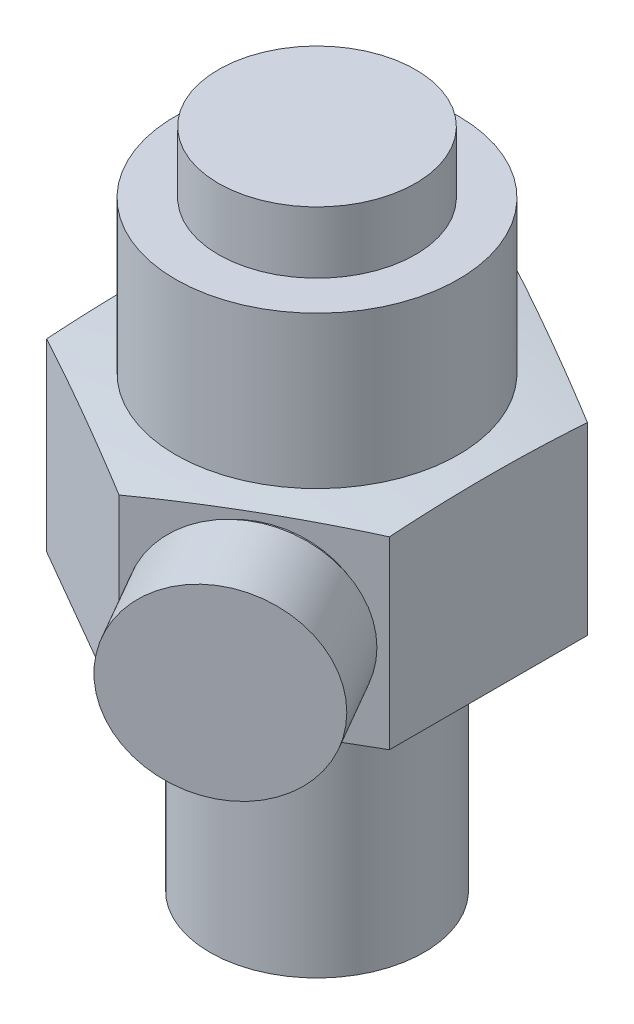
SolidWorks part; units mm, degrees
material "Brass"
ref_plane "Front Plane" through (0, 0, 0) normal (0, 0, 1) x (1, 0, 0)
ref_plane "Top Plane" through (0, 0, 0) normal (0, 1, 0) x (1, 0, 0)
ref_plane "Right Plane" through (0, 0, 0) normal (1, 0, 0) x (0, 0, -1)
sketch "Sketch1" plane through (0, 0, 0) normal (1, 0, 0) x (0, 0, -1)
  line L0 (10.4775, 33.1957) -> (10.4775, 44.45)
  line L1 (0, 0) -> (7.9375, 0)
  line L2 (0, 0) -> (0, 44.45)
  line L3 (0, 44.45) -> (10.4775, 44.45)
  line L4 (7.9375, 0) -> (7.9375, 19.05)
  line L5 (7.9375, 19.05) -> (25.4, 19.05)
  line L8 (25.4, 19.05) -> (25.4, 30.5116)
  arc A0 (10.4775, 33.1957) -> (25.4, 30.5116) centre (2.3997, -54.5366) cw
  dimension "D1" = 7.9375
  dimension "D2" = 19.05
  dimension "D5" = 10.4775
  dimension "D6" = 25.4
revolve "Revolve1" add sketch "Sketch1" angle 360 about L2
sketch "Sketch2" plane through (0, 0, 0) normal (0, 1, 0) x (1, 0, 0)
  line L0 (-12.7, 7.3323) -> (0, 14.6647)
  line L1 (0, 14.6647) -> (12.7, 7.3323)
  line L2 (12.7, 7.3323) -> (12.7, -7.3323)
  line L3 (12.7, -7.3323) -> (0, -14.6647)
  line L4 (0, -14.6647) -> (-12.7, -7.3323)
  line L5 (-12.7, 7.3323) -> (-12.7, -7.3323)
  line L6 (-12.7, 7.3323) -> (12.7, -7.3323) construction
  line L7 (-12.7, -7.3323) -> (12.7, 7.3323) construction
  line L8 (0, 14.6647) -> (0, -14.6647) construction
  circle A0 centre (0, 0) radius 12.7 construction
  circle A1 centre (0, 0) radius 31.2849
  dimension "D1" = 25.4
  dimension "D2" = 120
extrude "Cut-Extrude2" cut sketch "Sketch2" along normal through all
sketch "Sketch3" plane through (-6.35, 0, -10.9985) normal (-0.5, 0, -0.866) x (-0.866, 0, 0.5)
  circle A0 centre (0, 26.3074) radius 3.175
  dimension "D1" = 6.35
extrude "Boss-Extrude1" add sketch "Sketch3" along normal blind 6.35
sketch "Sketch4" plane through (6.35, 0, 10.9985) normal (0.5, 0, 0.866) x (0.866, 0, -0.5)
  circle A0 centre (0, 26.0448) radius 6.35
extrude "Boss-Extrude3" add sketch "Sketch4" along normal blind 6.35
sketch "Sketch5" plane through (9.525, 0, 16.4978) normal (0.5, 0, 0.866) x (0.866, 0, -0.5)
  circle A0 centre (0, 26.0448) radius 6.35 construction
  circle A1 centre (0, 26.0448) radius 6.35
  circle A2 centre (0, 26.0448) radius 6.604
  circle A3 centre (0, 26.0448) radius 6.858
  dimension "D1" = 0.254
  dimension "D2" = 0.254
extrude "Boss-Extrude4" add sketch "Sketch5" along normal blind 0.508 and the other way blind 5.588 separate body contours A3 | A2
extrude "Boss-Extrude5" add sketch "Sketch5<3>" along normal blind 0.508 contours A2
sketch "Sketch5<3>" plane through (9.525, 0, 16.4978) normal (0.5, 0, 0.866) x (0.866, 0, -0.5) same geometry as "Sketch5"
sketch "Sketch6" plane through (0, 44.45, 0) normal (0, 1, 0) x (1, 0, 0)
  circle A0 centre (0, 0) radius 7.3025
  dimension "D1" = 14.605
extrude "Boss-Extrude6" add sketch "Sketch6" along normal blind 4.572
